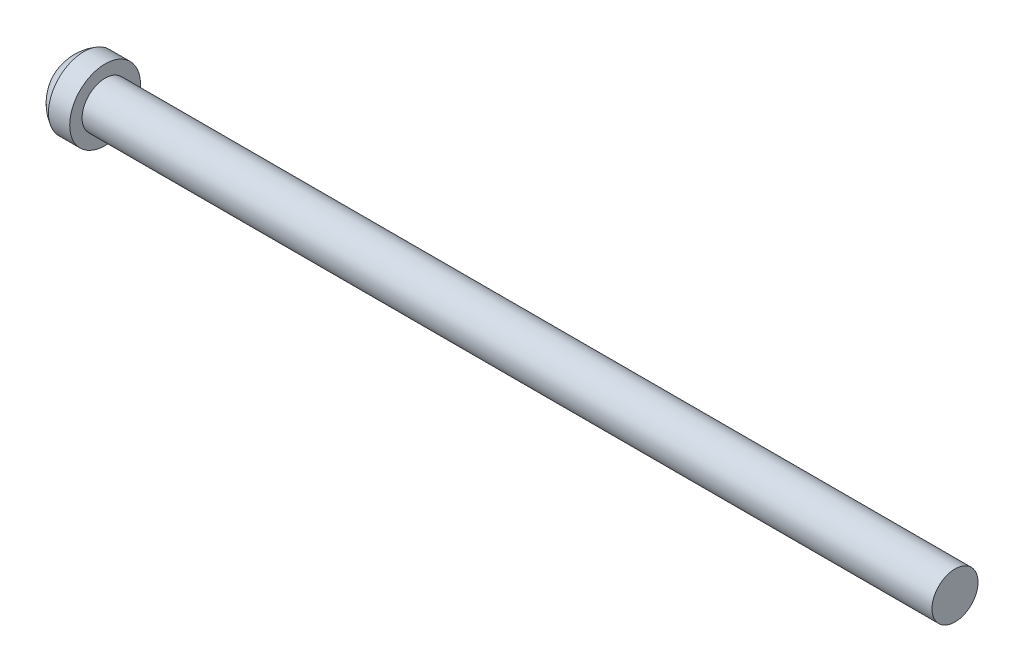
SolidWorks part; units mm, degrees
ref_plane "Ebene vorne" through (0, 0, 0) normal (1, 0, 0) x (0, 1, 0)
ref_plane "Ebene oben" through (0, 0, 0) normal (0, 0, 1) x (0, 1, 0)
ref_plane "Ebene rechts" through (0, 0, 0) normal (0, 1, 0) x (-1, 0, 0)
sketch "Skizze1" plane through (0, 0, 0) normal (1, 0, 0) x (0, 1, 0)
  circle A2 centre (-60, 5) radius 3.25
  circle A3 centre (-60, 5) radius 3.25
  dimension "D1" = 0.25
sketch "Skizze2" plane through (-60, 0, 0) normal (0, 0, 1) x (-1, 0, 0)
  line L0 (60, 31.5612) -> (-60, 31.5612) construction
  line L1 (60, 31.5612) -> (-60, 31.5612)
sketch "Skizze3" plane through (-120, 0, 0) normal (-1, 0, 0) x (0, -1, 0)
  circle A2 centre (60, 5) radius 3.25
  circle A3 centre (60, 5) radius 3.25
  dimension "D1" = 0.25
sweep "Austragung1" add profiles "Skizze3" path "Skizze2"
sketch "Skizze4" plane through (-120, 0, 0) normal (-1, 0, 0) x (0, -1, 0)
  circle A0 centre (60, 5) radius 5
extrude "Aufsatz-Linear austragen3" add sketch "Skizze4" along normal blind 3
dome "Kuppel1" faces to dome 1 distance 3 reverse direction no elliptical dome no face at (-123, -60, 10) parameters "D1"=3
